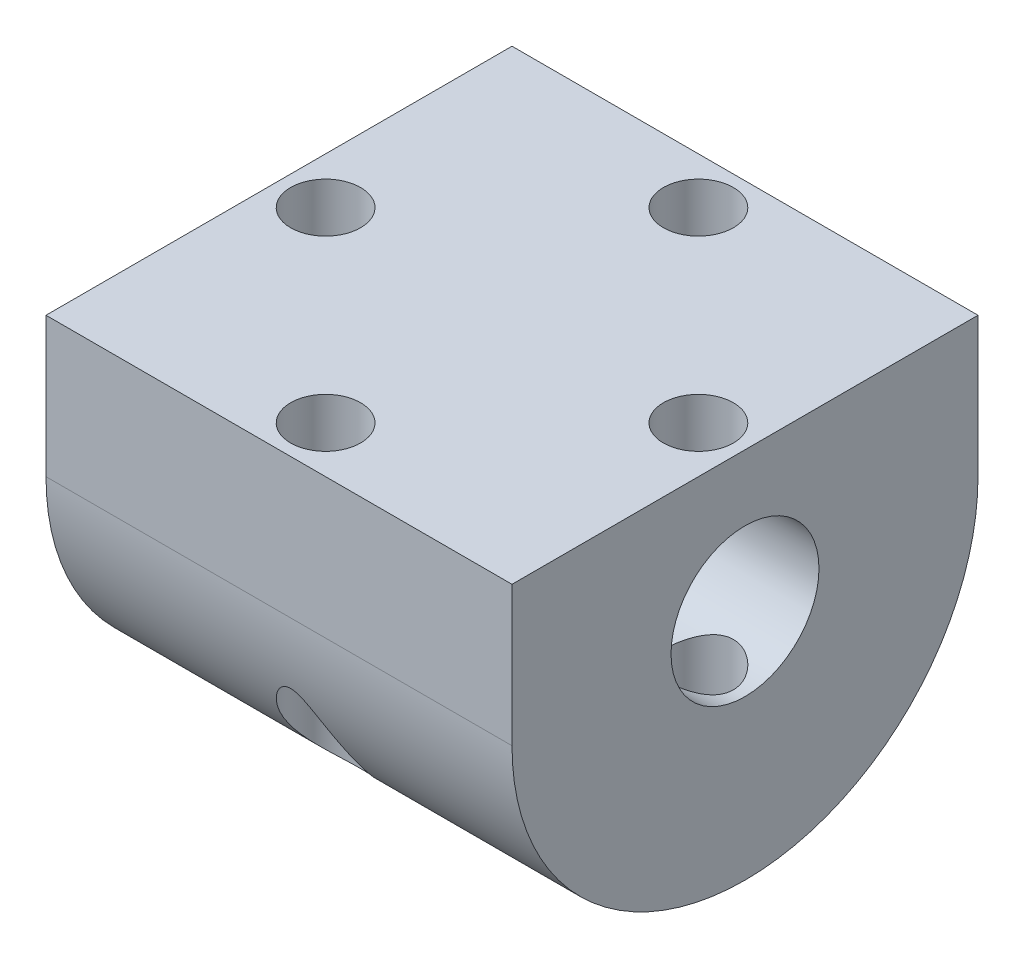
SolidWorks part; units mm, degrees
material "ABS"
ref_plane "Front Plane" through (0, 0, 0) normal (0, 0, 1) x (1, 0, 0)
ref_plane "Top Plane" through (0, 0, 0) normal (0, 1, 0) x (1, 0, 0)
ref_plane "Right Plane" through (0, 0, 0) normal (1, 0, 0) x (0, 0, -1)
sketch "Sketch1" plane through (0, 0, 0) normal (0, 1, 0) x (1, 0, 0)
  line L1 (-10, 0) -> (10, 0)
  line L2 (-10, 0) -> (-10, -20)
  line L3 (-10, -20) -> (10, -20)
  line L4 (10, 0) -> (10, -20)
  circle A0 centre (0, -10) radius 8
  circle A1 centre (8, -10) radius 1.5
  circle A2 centre (0, -18) radius 1.5
  circle A3 centre (-8, -10) radius 1.5
  circle A4 centre (0, -2) radius 1.5
  point P18 (0, -10)
  dimension "D3" = 16
  dimension "D6" = 3
  dimension "D1" = 20
  dimension "D2" = 20
  dimension "D4" = 10
  dimension "D5" = 10
  dimension "D7" = 4
extrude "Boss-Extrude1" add sketch "Sketch1" along normal blind 2.5 contours A4 A0 A3 A2 A1 | L4 L1 L2 L3 A4 A0 A1 A2 A3 | A0 A1 | A0 A2 | A0 A2 | A0 A3 | A0 A3 | A0 A1 | A4 region at (0, 0, 0.2828) region at (7.3387, 0, 10) region at (8.6106, 0, 10) region at (0, 0, 10) region at (0, 0, 18.6106) region at (0, 0, 17.3387) region at (-7.3387, 0, 10) region at (-8.6106, 0, 10)
sketch "Sketch2" plane through (-10, 0, 0) normal (-1, 0, 0) x (0, 0, 1)
  line L1 (0, 0) -> (20, 0)
  line L2 (0, 0) -> (0, -3.5)
  line L4 (20, 0) -> (20, -3.5)
  arc A0 (0, -3.5) -> (20, -3.5) centre (10, -3.5) ccw
  circle A1 centre (10, -3.5) radius 3.175
  dimension "D3" = 10
  dimension "D4" = 6.35
  dimension "D1" = 3.5
  dimension "D2" = 20
extrude "Boss-Extrude2" add sketch "Sketch2" against normal up to surface (20 mm away) up to face at (10, 1.25, 10)
extrude "Cut-Extrude2" cut sketch "Sketch1<3>" against normal through all both and the other way through all contours A0 A4 | A0 A4 | A0 A1 | A0 A1 | A0 A2 | A0 A2 | A0 A3 | A0 A3 region at (7.3387, 0, 10) region at (8.6106, 0, 10) region at (0, 0, 2.6613) region at (0, 0, 1.3894) region at (0, 0, 18.6106) region at (0, 0, 17.3387) region at (-7.3387, 0, 10) region at (-8.6106, 0, 10)
sketch "Sketch1<3>" plane through (0, 0, 0) normal (0, 1, 0) x (1, 0, 0) same geometry as "Sketch1"
